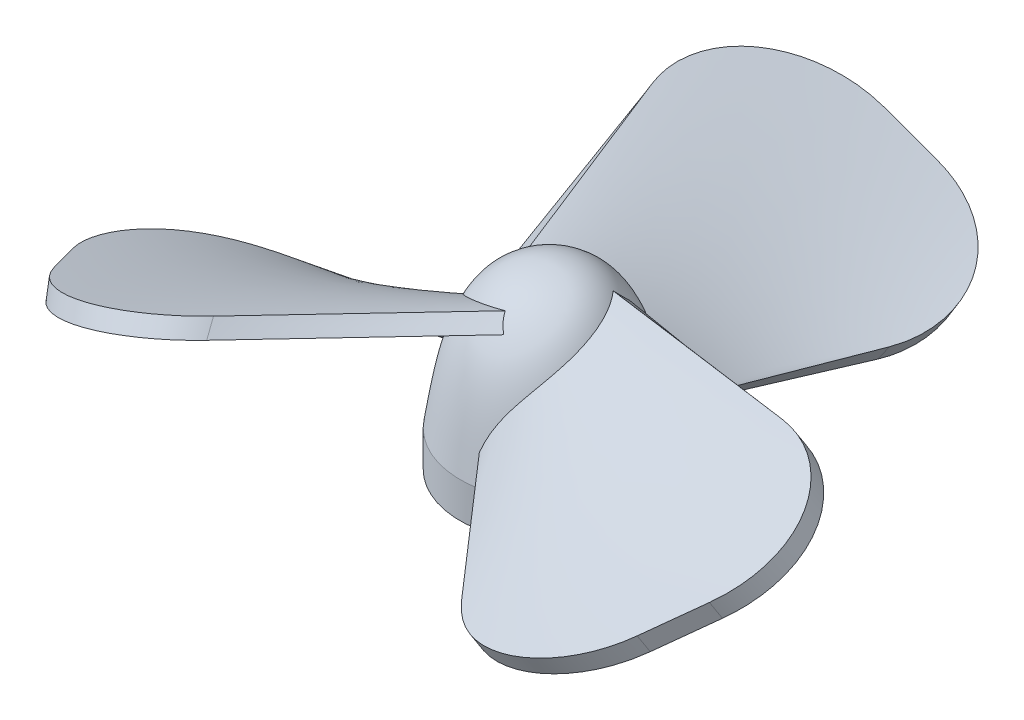
SolidWorks part; units mm, degrees
ref_plane "前基準面" through (0, 0, 0) normal (0, 0, 1) x (1, 0, 0)
ref_plane "上基準面" through (0, 0, 0) normal (0, 1, 0) x (1, 0, 0)
ref_plane "右基準面" through (0, 0, 0) normal (1, 0, 0) x (0, 0, -1)
sketch "草圖1" plane through (0, 0, 0) normal (0, 0, 1) x (1, 0, 0)
  line L0 (0, 0) -> (0, 7.2909) construction
  line L1 (5, 0) -> (0, 0)
  line L3 (0, 8) -> (0, 0)
  spline S0 degree 3 poles (0, 8) (3.9326, 7.9255) (4.4056, 3.793) (5, 0) knots 0 0 0 0 1 1 1 1
  dimension "D2" = 8
revolve "旋轉1" add sketch "草圖1" angle 360 about L0
sketch "草圖3" plane through (0, 0, 0) normal (1, 0, 0) x (0, 0, -1)
  line L0 (0, 0) -> (0, 8) construction
  line L1 (0, 7.5) -> (0, 0.5)
  line L2 (-5, 0) -> (5, 0) construction
  line L3 (0, 4) -> (20, 4) construction
  dimension "D1" = 7
  dimension "D2" = 0.5
  dimension "D3" = 20
ref_plane "平面1" through (0, 4, 0) normal (0, 1, 0) x (1, 0, 0)
ref_plane "平面2" through (0, 0, -20) normal (0, 0, -1) x (-1, 0, 0)
sketch "草圖7" plane through (0, 0, -20) normal (0, 0, -1) x (-1, 0, 0)
  line L0 (0, 4) -> (7.1934, 4) construction
  line L3 (-9.2259, 0.11) -> (9.5679, 6.9504)
  line L4 (-9.2259, 0.11) -> (-9.5679, 1.0496)
  line L5 (9.5679, 6.9504) -> (9.2259, 7.89)
  line L6 (-9.5679, 1.0496) -> (9.2259, 7.89)
  line L7 (-9.2259, 0.11) -> (9.2259, 7.89) construction
  line L8 (9.5679, 6.9504) -> (-9.5679, 1.0496) construction
  point P0 (0, 4)
  point P3 (0, 4)
  dimension "D1" = 1
  dimension "D2" = 20
  dimension "D3" = 20
sketch "草圖8" plane through (0, 0, 0) normal (0, 0, 1) x (1, 0, 0)
  line L0 (0, 7.5) -> (0, 0.5) construction
  line L1 (-1.8667, 7.0025) -> (-2.6328, 6.3598)
  line L2 (-1.8667, 7.0025) -> (2.6328, 1.6402) construction
  line L3 (2.6328, 1.6402) -> (1.8667, 0.9975)
  line L4 (-2.6328, 6.3598) -> (1.8667, 0.9975) construction
  line L5 (-1.8667, 7.0025) -> (1.8667, 0.9975) construction
  line L6 (2.6328, 1.6402) -> (-2.6328, 6.3598) construction
  line L7 (0.383, 4.3214) -> (2.3851, 6.0014) construction
  spline S0 degree 2 poles (1.8667, 0.9975) (1.6191, 5.3586) (-2.6328, 6.3598) knots 0 0 0 1 1 1
  spline S1 degree 2 poles (2.6328, 1.6402) (2.3851, 6.0014) (-1.8667, 7.0025) knots 0 0 0 1 1 1
  point P0 (0, 4)
  point P7 (-1.0369, 3.1299)
  point P12 (-0.5131, 3.4724)
  point P13 (2.7365, 1.6402)
  point P15 (0, 0)
  point P16 (1.0481, 4.8795)
  point P17 (2.3851, 6.0014)
  dimension "D1" = 7
  dimension "D2" = 1
  dimension "D3" = 40
  dimension "D4" = 1
loft "疊層拉伸5" add profiles "草圖8", "草圖7" connector at (-2.6328, 6.3598, 0) connector at (-9.5679, 6.9504, -20)
sketch "草圖5" plane through (0, 0, 0) normal (0, 0, 1) x (1, 0, 0)
  line L0 (0, 13.8135) -> (0, -9.1527) construction
fillet "圓角1" radius 6 2 edges
pattern_circular "環狀複製排列1" count 3 every 120 about axis through (0, 7.5, 0) along (0, -1, 0) of "疊層拉伸5", "圓角1"
sketch "草圖2" plane through (0, 0, 0) normal (0, -1, 0) x (1, 0, 0)
  circle A0 centre (0, 0) radius 1.175
  dimension "D1" = 2.35
extrude "除料-伸長2" cut sketch "草圖2" against normal blind 5 contours A0
sketch "草圖9" plane through (0, 0, 0) normal (0, -1, 0) x (1, 0, 0)
  circle A0 centre (0, 0) radius 5 construction
  circle A1 centre (0, 0) radius 1.175
  circle A2 centre (0, 0) radius 1.175
  circle A3 centre (0, 0) radius 5
  dimension "D1" = 0
extrude "填料-伸長1" add sketch "草圖9" along normal blind 2
